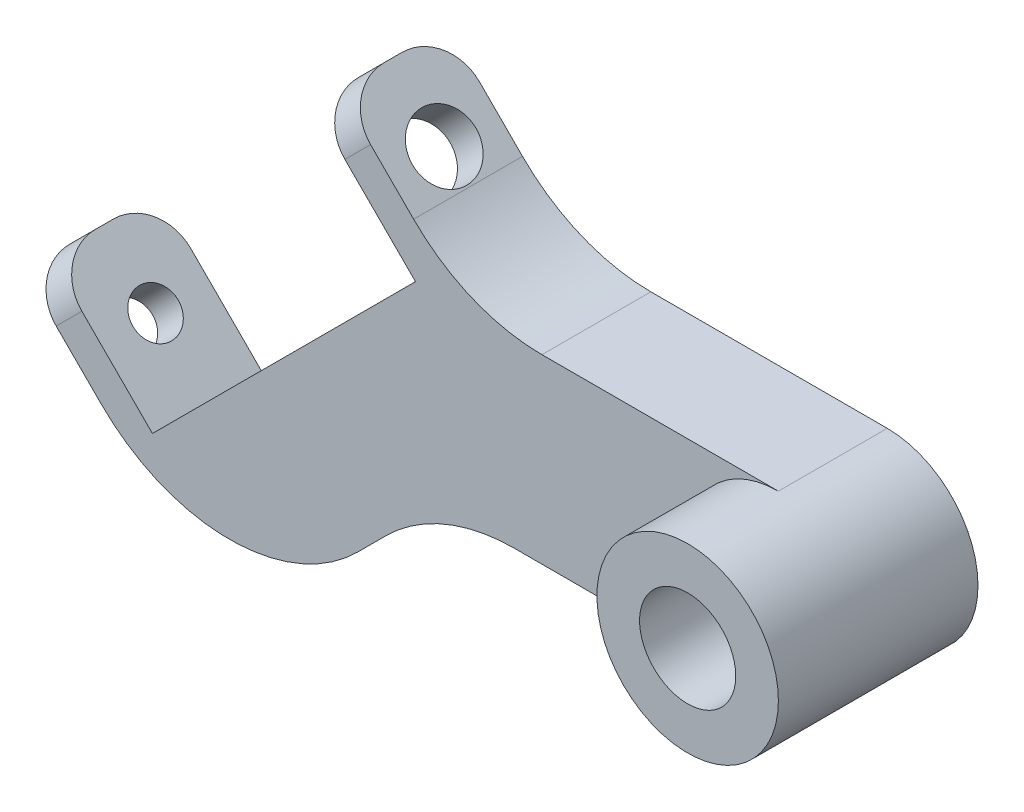
SolidWorks part; units mm, degrees
ref_plane "Piano frontale" through (0, 0, 0) normal (0, 0, 1) x (1, 0, 0)
ref_plane "Piano superiore" through (0, 0, 0) normal (0, 1, 0) x (1, 0, 0)
ref_plane "Piano destro" through (0, 0, 0) normal (1, 0, 0) x (0, 0, -1)
sketch "Schizzo1" plane through (0, 0, 0) normal (0, 0, 1) x (1, 0, 0)
  line L0 (0, 0) -> (-20, 0)
  line L1 (-20, 0) -> (-10, 10)
  line L2 (-10, 10) -> (10, 10)
  line L4 (10, 0) -> (0, 0)
  arc A0 (10, 0) -> (10, 10) centre (10, 5) ccw
  dimension "D6" = 10
  dimension "D1" = 20
  dimension "D2" = 10
  dimension "D3" = 10
  dimension "D4" = 0
  dimension "D5" = 20
extrude "Estrusione-Estrusione1" add sketch "Schizzo1" along normal blind 6 contours L2 A0 L4 L0 L1
sketch "Schizzo3" plane through (0, 0, 6) normal (0, 0, 1) x (1, 0, 0)
  arc A0 (10, 0) -> (10, 10) centre (10, 5) ccw construction
  arc A1 (10, 0) -> (10, 10) centre (10, 5) ccw construction
  circle A2 centre (10, 5) radius 5
  circle A3 centre (10, 5) radius 2.65
  dimension "D1" = 5.3
extrude "Estrusione-Estrusione3" add sketch "Schizzo3" along normal blind 5
sketch "Schizzo4" plane through (0, 0, 6) normal (0, 0, 1) x (1, 0, 0)
  line L0 (-10, 10) -> (-16.0795, 16.0795)
  line L1 (-20, 0) -> (-10, 10) construction
ref_plane "Piano1" through (0, 0, 0) normal (0.7071, 0.7071, 0) x (-0.7071, 0.7071, 0)
sketch "Schizzo5" plane through (0, 0, 0) normal (0.7071, 0.7071, 0) x (-0.7071, 0.7071, 0)
  line L0 (14.1421, 3) -> (18.1421, 3)
  line L1 (14.1421, 6) -> (14.1421, 0) construction
  circle A0 centre (18.1421, 3) radius 0.925
  dimension "D2" = 1.85
  dimension "D1" = 4
extrude "Estrusione-Estrusione4" add sketch "Schizzo5" against normal blind 20 separate body contours A0 region at (-12.8284, 12.8284, 2.1012)
sketch "Schizzo12" plane through (0, 0, 0) normal (0.7071, 0.7071, 0) x (-0.7071, 0.7071, 0)
  line L0 (14.1421, 0) -> (0, 0) construction
  line L1 (14.1421, 6) -> (22.1421, 6)
  line L2 (14.1421, 6) -> (14.1421, 0)
  line L3 (14.1421, 0) -> (22.1421, 0)
  line L4 (22.1421, 6) -> (22.1421, 0)
  dimension "D1" = 8
extrude "Estrusione-Estrusione6" add sketch "Schizzo12" along normal blind 2
sketch "Schizzo13" plane through (-10, 10, 0) normal (0.7071, -0.7071, 0) x (0, 0, -1)
  line L4 (-6, 0) -> (0, 0)
  line L5 (0, 0) -> (0, 2)
  line L6 (0, 2) -> (-6, 2)
  line L7 (-6, 2) -> (-6, 0)
  line L8 (-6, 0) -> (0, 0)
  line L9 (0, 0) -> (0, 2)
  line L10 (0, 2) -> (-6, 2)
  line L11 (-6, 2) -> (-6, 0)
  dimension "D1" = 0
extrude "Estrusione-Estrusione7" add sketch "Schizzo13" along normal blind 3
fillet "Raccordo2" radius 2.5 2 edges at (-14.9497, 16.364, 0) (-14.9497, 16.364, 6)
sketch "Schizzo14" plane through (1.4142, 1.4142, 0) normal (0.7071, 0.7071, 0) x (0, 0, -1)
  circle A0 centre (-3, 18.1421) radius 1.75
  circle A1 centre (-3, 18.1421) radius 0.925
  circle A2 centre (-3, 18.1421) radius 0.925
  dimension "D2" = 3.5
  dimension "D1" = 0
extrude "Taglio-Estrusione7" cut sketch "Schizzo14" against normal blind 25 contours A2 | A0 A2 | A2 | A0 region at (-11.4142, 14.2426, 4.7005) region at (-11.4142, 14.2426, 3)
sketch "Schizzo15" plane through (0, 0, 0) normal (-0.7071, -0.7071, 0) x (0, 0, 1)
  line L0 (0, 14.1421) -> (0, 19.6421) construction
  line L1 (6, 14.1421) -> (0, 14.1421)
  line L2 (6, 14.1421) -> (6, 6.1421)
  line L3 (6, 6.1421) -> (0, 6.1421)
  line L4 (0, 14.1421) -> (0, 6.1421)
  dimension "D1" = 8
extrude "Estrusione-Estrusione8" add sketch "Schizzo15" along normal blind 22.5
sketch "Schizzo16" plane through (-10, 10, 0) normal (-0.7071, 0.7071, 0) x (0, 0, 1)
  line L0 (0, -22.5) -> (0, 0) construction
  line L1 (6, -22.5) -> (0, -22.5)
  line L2 (6, -22.5) -> (6, -20.5)
  line L3 (6, -20.5) -> (0, -20.5)
  line L4 (0, -22.5) -> (0, -20.5)
  dimension "D1" = 2
extrude "Estrusione-Estrusione9" add sketch "Schizzo16" along normal up to vertex up to point (-15.6569, 15.6569, 2.5)
sketch "Schizzo17" plane through (-15.9099, -15.9099, 0) normal (-0.7071, -0.7071, 0) x (0, 0, 1)
  circle A0 centre (3, 18.1421) radius 1.75 construction
  circle A1 centre (3, 18.1421) radius 1.75
  circle A2 centre (3, 18.1421) radius 1.25
  dimension "D1" = 2.5
extrude "Taglio-Estrusione8" cut sketch "Schizzo17" against normal blind 25 contours A2
fillet "Raccordo3" radius 10 1 edges at (-20.253, -11.5668, 3)
fillet "Raccordo4" radius 10 1 edges at (-8.6863, 0, 3)
fillet "Raccordo5" radius 10 1 edges at (-7.1716, 10, 3)
fillet "Raccordo6" radius 2.5 2 edges at (-30.8597, 0.4541, 0) (-30.8597, 0.4541, 6)
sketch "Schizzo18" plane through (0, 0, 6) normal (0, 0, 1) x (1, 0, 0)
  circle A0 centre (10, 5) radius 1.75
  dimension "D1" = 3.5
extrude "Taglio-Estrusione9" cut sketch "Schizzo18" against normal through all
ref_axis "Assi1" through (-14.0659, 11.591, 3) along (0.7071, 0.7071, 0)
ref_axis "Assi2" through (-13.8891, 13.8891, 6) along (0.7071, -0.7071, 0)
ref_axis "Assi3" through (-10.1005, 12.9289, 6) along (0, 0, -1)
ref_point "Punto1"
ref_point "Punto2"
ref_axis "Assi4" through (10, 5, 11) along (0, 0, -1)
ref_axis "Assi5" through (-3.0294, 10, 6) along (1, 0, 0)
